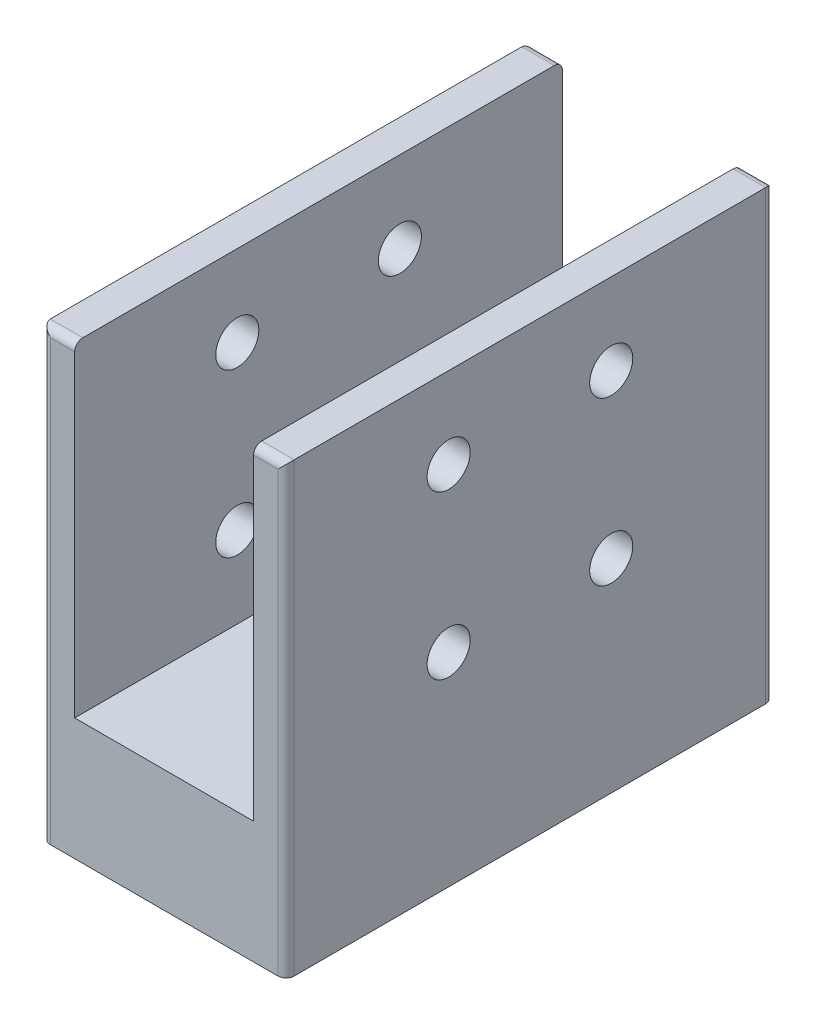
SolidWorks part; units mm, degrees
material "ABS"
ref_plane "Front Plane" through (0, 0, 0) normal (0, 0, 1) x (1, 0, 0)
ref_plane "Top Plane" through (0, 0, 0) normal (0, 1, 0) x (1, 0, 0)
ref_plane "Right Plane" through (0, 0, 0) normal (1, 0, 0) x (0, 0, -1)
sketch "Sketch1" plane through (0, 0, 0) normal (0, 1, 0) x (1, 0, 0)
  line L1 (-15, 30) -> (15, 30)
  line L2 (-15, 30) -> (-15, -30)
  line L3 (-15, -30) -> (15, -30)
  line L4 (15, 30) -> (15, -30)
  line L5 (-10, 20) -> (10, 20) construction
  line L6 (-10, 20) -> (-10, -20) construction
  line L7 (-10, -20) -> (10, -20) construction
  line L8 (10, 20) -> (10, -20) construction
  line L9 (0, 10) -> (0, -10) construction
  line L10 (-15, 30) -> (-11, 30)
  line L11 (-15, 30) -> (-15, -30)
  line L12 (-15, -30) -> (-11, -30)
  line L13 (-11, 30) -> (-11, -30)
  line L14 (11, 30) -> (15, 30)
  line L15 (11, 30) -> (11, -30)
  line L16 (11, -30) -> (15, -30)
  line L17 (15, 30) -> (15, -30)
  circle A1 centre (0, 10) radius 2.5
  circle A2 centre (0, -10) radius 2.5
  point P7 (0, 30)
  point P8 (-15, 0)
  point P13 (0, 20)
  point P14 (-10, 0)
  point P17 (0, 0)
  point P20 (15, 0)
  dimension "D1" = 5
  dimension "D2" = 30
  dimension "D3" = 60
  dimension "D4" = 20
  dimension "D5" = 40
  dimension "D6" = 20
  dimension "D7" = 4
extrude "Boss-Extrude1" add sketch "Sketch1" against normal blind 15 contours L15 L1 L13 L3 A2 A1 | L13 L1 L2 L3 | L1 L15 L3 L4 region at (-13, 0, 0) region at (0, 0, 0) region at (13, 0, 0)
extrude "Boss-Extrude2" add sketch "Sketch1<3>" along normal blind 40 contours L13 L1 L2 L3 | L1 L15 L3 L4 region at (-13, 0, 0) region at (13, 0, 0)
sketch "Sketch1<3>" plane through (0, 0, 0) normal (0, 1, 0) x (1, 0, 0) same geometry as "Sketch1"
sketch "Sketch3" plane through (15, 0, 0) normal (1, 0, 0) x (0, 0, -1)
  line L0 (-10, 10) -> (10, 10) construction
  circle A0 centre (-10, 10) radius 2.5 construction
  circle A1 centre (10, 10) radius 2.5 construction
  point P4 (0, 10)
  point P5 (10, 21.6081)
  dimension "D3" = 5
  dimension "D1" = 20
  dimension "D2" = 10
hole_wizard "M5 Clearance Hole1" positions "3DSketch1" profile "Sketch5" hole size "M5" standard "ANSI Metric" end condition through all
sketch3d "3DSketch1"
  point P0 (15, 10, 10)
  point P2 (15, 10, -10)
  point P5 (15, 20, -10)
  point P7 (15, 20, 10)
sketch "Sketch5" plane through (15, 10, 10) normal (0, 1, 0) x (0, 0, -1)
  line L0 (0, 0) -> (0, 30)
  line L1 (0, 30) -> (2.65, 30)
  line L2 (2.65, 30) -> (2.65, 0)
  line L5 (2.65, 0) -> (0, 0)
  line L11 (0, -6.35) -> (0, 107.95) construction
  dimension "Thru Hole Dia." = 5.3
  dimension "Thru Hole Depth" = 30
pattern_linear "LPattern1" count 2 spacing 20 along (0, 1, 0) of "M5 Clearance Hole1"
fillet "Fillet1" radius 1 8 edges at (-15, 12.5, -30) (15, 12.5, -30) (15, 12.5, 30) (-15, 12.5, 30) (13, 40, 30) (13, 40, -30) (-13, 40, -30) (-13, 40, 30)
